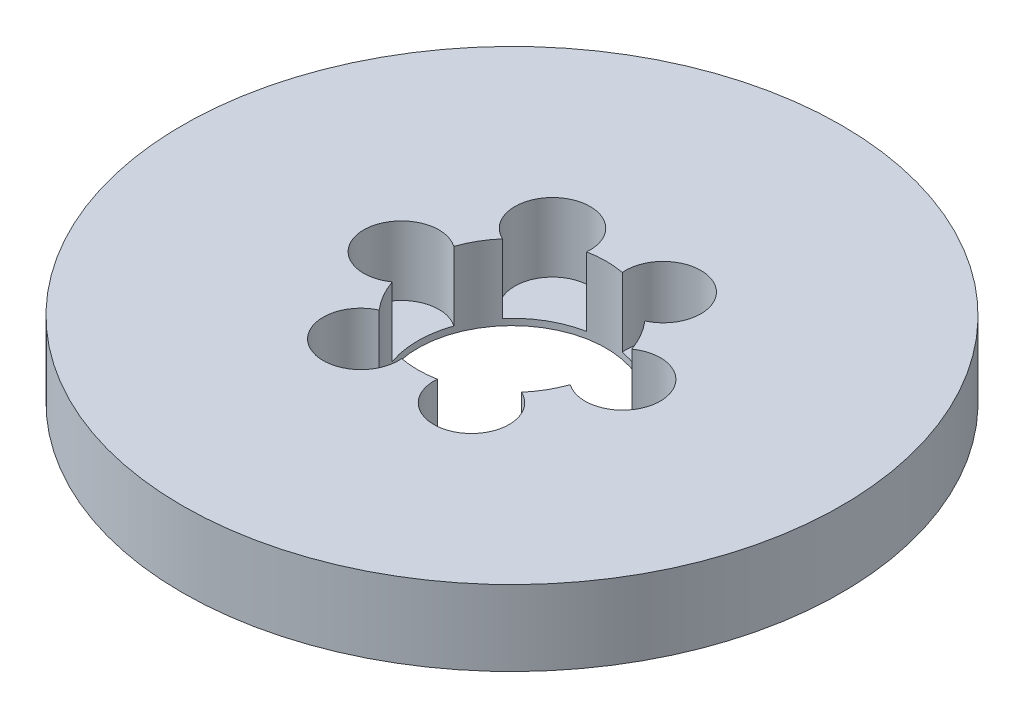
SolidWorks part; units mm, degrees
ref_plane "Front Plane" through (0, 0, 0) normal (0, 0, 1) x (1, 0, 0)
ref_plane "Top Plane" through (0, 0, 0) normal (0, 1, 0) x (1, 0, 0)
ref_plane "Right Plane" through (0, 0, 0) normal (1, 0, 0) x (0, 0, -1)
sketch "Sketch1" plane through (0, 0, 0) normal (0, 1, 0) x (1, 0, 0)
  circle A0 centre (0, 0) radius 87.5
  dimension "FLANGE_OD" = 175
extrude "Boss-Extrude1" add sketch "Sketch1" along normal blind 20
sketch "Sketch2" plane through (0, 0, 0) normal (0, 1, 0) x (1, 0, 0)
  circle A0 centre (0, 0) radius 25
  dimension "BORE_D" = 50
extrude "Cut-Extrude1" cut sketch "Sketch2" along normal through all
sketch "Sketch3" plane through (0, 20, 0) normal (0, 1, 0) x (1, 0, 0)
  circle A0 centre (0, 0) radius 29.385 construction
  circle A1 centre (-29.385, 0) radius 10
  dimension "BOLT_D" = 20
  dimension "BOLT_PCD" = 58.77
extrude "Cut-Extrude2" cut sketch "Sketch3" against normal blind 18.2984
pattern_circular "CirPattern1" count 6 over 360 about axis through (0, 0, 0) along (0, 1, 0) of "Cut-Extrude2"
